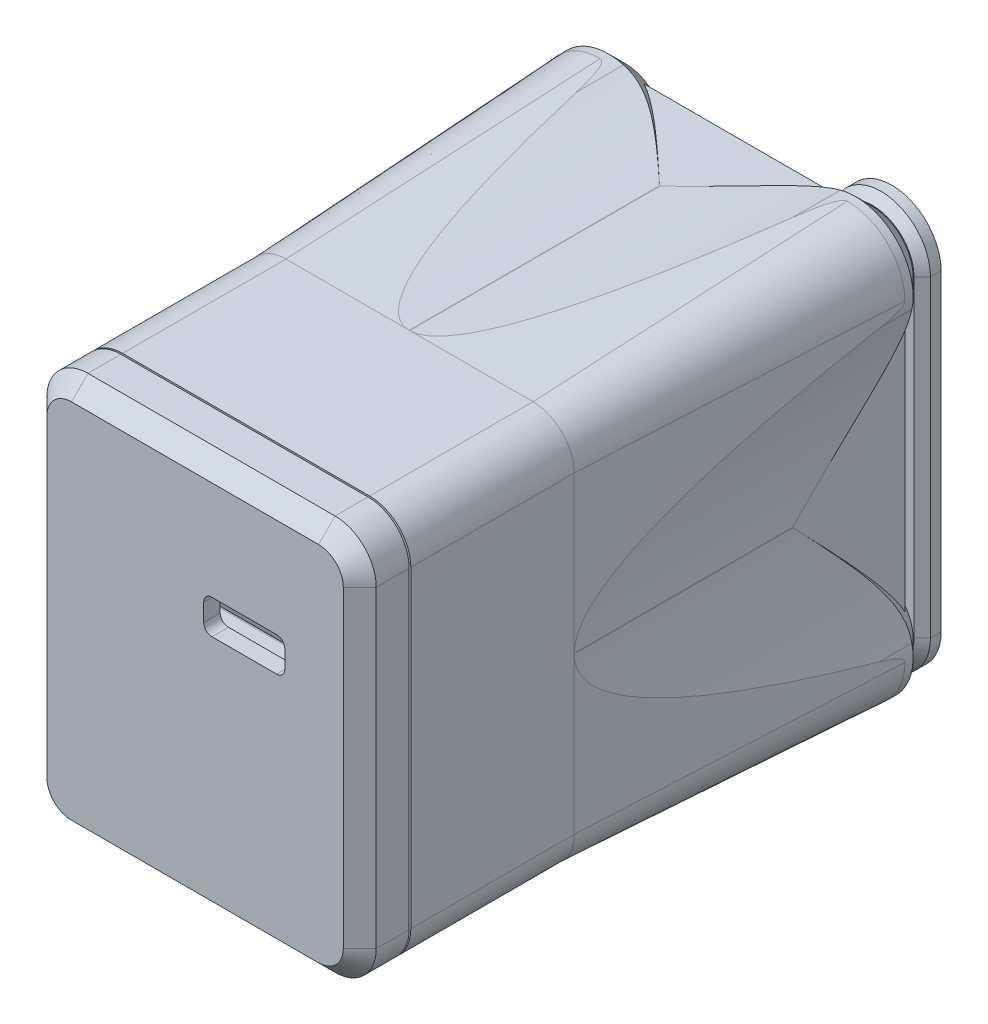
SolidWorks part; units mm, degrees
ref_plane "Front" through (0, 0, 0) normal (0, 0, 1) x (1, 0, 0)
ref_plane "Top" through (0, 0, 0) normal (0, 1, 0) x (1, 0, 0)
ref_plane "Right" through (0, 0, 0) normal (1, 0, 0) x (0, 0, -1)
sketch "Sketch2" plane through (0, 0, 0) normal (0, 0, 1) x (1, 0, 0)
  line L1 (-20, -24) -> (20, -24)
  line L2 (-20, -24) -> (-20, 24)
  line L3 (-20, 24) -> (20, 24)
  line L4 (20, -24) -> (20, 24)
  line L5 (-20, -24) -> (20, 24) construction
  line L6 (-20, 24) -> (20, -24) construction
  point P0 (0, 0)
  dimension "D1" = 48
  dimension "D2" = 40
extrude "Boss-Extrude1" add sketch "Sketch2" along normal blind 61
fillet "Fillet1" radius 5 4 edges at (-20, -24, 30.5) (20, -24, 30.5) (20, 24, 30.5) (-20, 24, 30.5)
shell "Shell1" thickness 3
sketch "Sketch3" plane through (0, 0, 3) normal (0, 0, 1) x (1, 0, 0)
  line L0 (6.4, -5.1945) -> (6.4, -0.3945)
  line L1 (-6, -4.7945) -> (6, -4.7945) construction
  line L2 (-6, -4.7945) -> (-6, -0.7945) construction
  line L3 (-6, -0.7945) -> (6, -0.7945) construction
  line L4 (6, -4.7945) -> (6, -0.7945) construction
  line L5 (-6, -4.7945) -> (6, -0.7945) construction
  line L6 (-6, -0.7945) -> (6, -4.7945) construction
  line L7 (-6.4, -0.3945) -> (6.4, -0.3945)
  line L8 (-6.4, -5.1945) -> (-6.4, -0.3945)
  line L9 (-6.4, -5.1945) -> (6.4, -5.1945)
  point P0 (0, -2.7945)
  dimension "D1" = 12
  dimension "D2" = 4
  dimension "D3" = 0.4
extrude "Cut-Extrude1" cut sketch "Sketch3" against normal through all contours L2 L1 L4 L3
sketch "Sketch4" plane through (0, 0, 3) normal (0, 0, 1) x (1, 0, 0)
  line L0 (-15, -21) -> (15, -21) construction
  line L1 (17, -21) -> (-17, -21)
  line L2 (17, -21) -> (17, 3.6055)
  line L3 (17, 3.6055) -> (-17, 3.6055)
  line L4 (-17, -21) -> (-17, 3.6055)
  line L5 (-17, 19) -> (-17, -19) construction
  line L6 (6.4, -0.3945) -> (-6.4, -0.3945) construction
  line L11 (6.4, -5.1945) -> (6.4, -0.3945)
  line L12 (6.4, -0.3945) -> (-6.4, -0.3945)
  line L13 (-6.4, -0.3945) -> (-6.4, -5.1945)
  line L14 (-6.4, -5.1945) -> (6.4, -5.1945)
  line L15 (6.4, -5.1945) -> (6.4, -0.3945)
  line L16 (6.4, -0.3945) -> (-6.4, -0.3945)
  line L17 (-6.4, -0.3945) -> (-6.4, -5.1945)
  line L18 (-6.4, -5.1945) -> (6.4, -5.1945)
  dimension "D1" = 4
  dimension "D2" = 0
extrude "Boss-Extrude2" add sketch "Sketch4" along normal blind 3
sketch "Sketch5" plane through (0, 0, 0) normal (0, 0, -1) x (-1, 0, 0)
  line L1 (-8.5, -7.4741) -> (8.5, -7.4741)
  line L2 (-8.5, -7.4741) -> (-8.5, 1.5259)
  line L3 (-8.5, 1.5259) -> (8.5, 1.5259)
  line L4 (-6.4, -0.3945) -> (-6.4, -5.1945)
  line L5 (6.4, -0.3945) -> (-6.4, -0.3945)
  line L6 (6.4, -5.1945) -> (6.4, -0.3945)
  line L7 (-6.4, -5.1945) -> (6.4, -5.1945)
  line L8 (-6.4, -0.3945) -> (-6.4, -5.1945)
  line L9 (6.4, -0.3945) -> (-6.4, -0.3945)
  line L10 (6.4, -5.1945) -> (6.4, -0.3945)
  line L11 (-6.4, -5.1945) -> (6.4, -5.1945)
  line L12 (8.5, -7.4741) -> (8.5, 1.5259)
  line L13 (-8.5, -7.4741) -> (8.5, 1.5259) construction
  line L14 (-8.5, 1.5259) -> (8.5, -7.4741) construction
  point P3 (0, -2.9741)
  dimension "D2" = 9
  dimension "D3" = 17
  dimension "D4" = 2.1
  dimension "D5" = 1.9204
  dimension "D1" = 0
extrude "Cut-Extrude2" cut sketch "Sketch5" against normal blind 4
chamfer "Chamfer1" distance 2 angle 45 4 edges at (0, 1.5259, 0) (-8.5, -2.9741, 0) (0, -7.4741, 0) (8.5, -2.9741, 0)
sketch "Sketch7" plane through (0, 0, 61) normal (0, 0, 1) x (1, 0, 0)
  line L1 (15, 20.6) -> (-15, 20.6)
  line L2 (-16.6, 19) -> (-16.6, -19)
  line L3 (-15, -20.6) -> (15, -20.6)
  line L4 (-20, 19) -> (-20, -19)
  line L5 (-15, -24) -> (15, -24)
  line L6 (20, -19) -> (20, 19)
  line L7 (15, 24) -> (-15, 24)
  line L8 (-20, 19) -> (-20, -19)
  line L9 (-15, -24) -> (15, -24)
  line L10 (20, -19) -> (20, 19)
  line L11 (15, 24) -> (-15, 24)
  line L12 (16.6, -19) -> (16.6, 19)
  line L13 (-17, 19) -> (-17, -19)
  line L14 (15, 21) -> (-15, 21)
  line L15 (17, -19) -> (17, 19)
  line L16 (-15, -21) -> (15, -21)
  line L17 (-17, 19) -> (-17, -19)
  line L18 (15, 21) -> (-15, 21)
  line L19 (17, -19) -> (17, 19)
  line L20 (-15, -21) -> (15, -21)
  line L21 (14.6, 18.6) -> (-14.6, 18.6)
  line L22 (-14.6, 18.6) -> (-14.6, -18.6)
  line L23 (-14.6, -18.6) -> (14.6, -18.6)
  line L24 (14.6, -18.6) -> (14.6, 18.6)
  arc A0 (-15, 20.6) -> (-16.6, 19) centre (-15, 19) ccw
  arc A1 (-16.6, -19) -> (-15, -20.6) centre (-15, -19) ccw
  arc A2 (15, -20.6) -> (16.6, -19) centre (15, -19) ccw
  arc A3 (16.6, 19) -> (15, 20.6) centre (15, 19) ccw
  arc A4 (-20, -19) -> (-15, -24) centre (-15, -19) ccw
  arc A5 (15, -24) -> (20, -19) centre (15, -19) ccw
  arc A6 (20, 19) -> (15, 24) centre (15, 19) ccw
  arc A7 (-15, 24) -> (-20, 19) centre (-15, 19) ccw
  arc A8 (-20, -19) -> (-15, -24) centre (-15, -19) ccw
  arc A9 (15, -24) -> (20, -19) centre (15, -19) ccw
  arc A10 (20, 19) -> (15, 24) centre (15, 19) ccw
  arc A11 (-15, 24) -> (-20, 19) centre (-15, 19) ccw
  arc A12 (-15, 21) -> (-17, 19) centre (-15, 19) ccw
  arc A13 (17, 19) -> (15, 21) centre (15, 19) ccw
  arc A14 (15, -21) -> (17, -19) centre (15, -19) ccw
  arc A15 (-17, -19) -> (-15, -21) centre (-15, -19) ccw
  arc A16 (-15, 21) -> (-17, 19) centre (-15, 19) ccw
  arc A17 (17, 19) -> (15, 21) centre (15, 19) ccw
  arc A18 (15, -21) -> (17, -19) centre (15, -19) ccw
  arc A19 (-17, -19) -> (-15, -21) centre (-15, -19) ccw
  arc A20 (-14.6, 18.6) -> (-14.6, 18.6) centre (-14.6, 18.6) ccw
  arc A21 (-14.6, -18.6) -> (-14.6, -18.6) centre (-14.6, -18.6) ccw
  arc A22 (14.6, -18.6) -> (14.6, -18.6) centre (14.6, -18.6) ccw
  arc A23 (14.6, 18.6) -> (14.6, 18.6) centre (14.6, 18.6) ccw
  dimension "D1" = 0
  dimension "D2" = 0
  dimension "D3" = 0.4
  dimension "D4" = 2
extrude "Boss-Extrude3" add sketch "Sketch7" against normal blind 3 and the other way blind 0.2 separate body contours L12 A3 L1 A0 L2 A1 L3 A2 A23 L24 A22 L23 A21 L22 A20 L21
sketch "Sketch8" plane through (0, 0, 61.2) normal (0, 0, 1) x (1, 0, 0)
  line L4 (-20, 19) -> (-20, -19)
  line L5 (-15, -24) -> (15, -24)
  line L6 (20, -19) -> (20, 19)
  line L7 (15, 24) -> (-15, 24)
  line L8 (-20, 19) -> (-20, -19)
  line L9 (-15, -24) -> (15, -24)
  line L10 (20, -19) -> (20, 19)
  line L11 (15, 24) -> (-15, 24)
  arc A4 (-20, -19) -> (-15, -24) centre (-15, -19) ccw
  arc A5 (15, -24) -> (20, -19) centre (15, -19) ccw
  arc A6 (20, 19) -> (15, 24) centre (15, 19) ccw
  arc A7 (-15, 24) -> (-20, 19) centre (-15, 19) ccw
  arc A8 (-20, -19) -> (-15, -24) centre (-15, -19) ccw
  arc A9 (15, -24) -> (20, -19) centre (15, -19) ccw
  arc A10 (20, 19) -> (15, 24) centre (15, 19) ccw
  arc A11 (-15, 24) -> (-20, 19) centre (-15, 19) ccw
  dimension "D1" = 0
extrude "Boss-Extrude4" add sketch "Sketch8" along normal blind 6
chamfer "Chamfer2" distance 2 angle 45 8 edges at (0, 24, 67.2) (20, 0, 67.2) (18.5355, 22.5355, 67.2) (18.5355, -22.5355, 67.2) (0, -24, 67.2) (-18.5355, 22.5355, 67.2) (-18.5355, -22.5355, 67.2) (-20, 0, 67.2)
fillet "Fillet2" radius 1 4 edges at (14.6, -18.6, 59.6) (14.6, 18.6, 59.6) (-14.6, -18.6, 59.6) (-14.6, 18.6, 59.6)
chamfer "Chamfer3" distance 3 angle 45 1 edges at (0, 3.6055, 3)
fillet "Fillet3" radius 3 1 edges at (0, 6.6055, 3)
sketch "Sketch9" plane through (0, 0, 61.2) normal (0, 0, -1) x (-1, 0, 0)
  line L0 (1.05, 9.9738) -> (10.9, 9.9738) construction
  line L1 (1.55, 6.3238) -> (10.4, 6.3238) construction
  line L2 (1.55, 6.3238) -> (1.55, 9.4738) construction
  line L3 (1.55, 9.4738) -> (10.4, 9.4738) construction
  line L4 (10.4, 6.3238) -> (10.4, 9.4738) construction
  line L5 (1.55, 6.3238) -> (10.4, 9.4738) construction
  line L6 (1.55, 9.4738) -> (10.4, 6.3238) construction
  line L7 (10.9, 5.8238) -> (10.9, 9.9738) construction
  line L8 (1.05, 5.8238) -> (10.9, 5.8238) construction
  line L9 (1.05, 5.8238) -> (1.05, 9.9738) construction
  line L10 (5.975, 7.8988) -> (-5.975, 7.8988) construction
  line L12 (-10.4, 6.3238) -> (-1.55, 6.3238) construction
  line L13 (-10.4, 6.3238) -> (-10.4, 9.4738) construction
  line L14 (-10.4, 9.4738) -> (-1.55, 9.4738) construction
  line L15 (-1.55, 6.3238) -> (-1.55, 9.4738) construction
  line L16 (-10.4, 6.3238) -> (-1.55, 9.4738) construction
  line L17 (-10.4, 9.4738) -> (-1.55, 6.3238) construction
  line L22 (-10.9, 5.8238) -> (-1.05, 5.8238)
  line L23 (-1.05, 5.8238) -> (-1.05, 9.9738)
  line L24 (-10.9, 9.9738) -> (-1.05, 9.9738)
  line L25 (-10.9, 5.8238) -> (-10.9, 9.9738)
  line L26 (0, 0) -> (0, 7.8988) construction
  point P0 (5.975, 7.8988)
  point P14 (-5.975, 7.8988)
  dimension "D1" = 3.15
  dimension "D2" = 8.85
  dimension "D4" = 3.15
  dimension "D5" = 8.85
  dimension "D7" = 20.8
  dimension "D3" = 0.5
  dimension "D6" = 0.5
extrude "Cut-Extrude3" cut sketch "Sketch9" against normal through all
fillet "Fillet4" radius 1 4 edges at (10.9, 5.8238, 64.2) (10.9, 9.9738, 64.2) (1.05, 9.9738, 64.2) (1.05, 5.8238, 64.2)
sketch "Sketch12" plane through (0, 0, 61.2) normal (0, 0, -1) x (-1, 0, 0)
  line L1 (-14.6, 3.8238) -> (14.6, 3.8238)
  line L2 (-14.6, 3.8238) -> (-14.6, 10.0951)
  line L3 (-14.6, 10.0951) -> (14.6, 10.0951)
  line L4 (14.6, 3.8238) -> (14.6, 10.0951)
  line L5 (-14.6, 3.8238) -> (14.6, 10.0951) construction
  line L6 (-14.6, 10.0951) -> (14.6, 3.8238) construction
  line L7 (-14.6, -17.6) -> (-14.6, 17.6) construction
  line L8 (14.6, 17.6) -> (14.6, -17.6) construction
  point P0 (0, 6.9595)
extrude "Cut-Extrude4" cut sketch "Sketch12" against normal offset from surface (4 mm away) 2 up to face at (5.975, 7.8988, 67.2)
chamfer "Chamfer4" distance 4 angle 45 1 edges at (0, 10.0951, 61.2)
fillet "Fillet5" radius 0.5 2 edges at (0, 14.0951, 61.2) (0, 3.8238, 61.2)
sketch "Sketch13" plane through (0, -24, 0) normal (0, -1, 0) x (1, 0, 0)
  line L0 (0, 0) -> (0, 48) construction
  line L1 (-2.6382, 42.5) -> (2.6382, 42.5)
  line L2 (-2.6382, 53.5) -> (2.6382, 53.5)
  circle A0 centre (0, 48) radius 6.1
  dimension "D1" = 12.2
  dimension "D2" = 11
  dimension "D3" = 48
extrude "Cut-Extrude5" cut sketch "Sketch13" against normal blind 4
sketch "Sketch14" plane through (0, 0, 0) normal (0, 0, -1) x (-1, 0, 0)
  circle A0 centre (15, 19) radius 3.25 construction
  circle A1 centre (15, 19) radius 3.65
  circle A2 centre (-15, 19) radius 3.65
  circle A3 centre (-15, -19) radius 3.65
  circle A4 centre (15, -19) radius 3.65
  dimension "D1" = 6.5
  dimension "D3" = 7.3
  dimension "D4" = 7.3
  dimension "D5" = 7.3
  dimension "D2" = 0.4
extrude "Cut-Extrude6" cut sketch "Sketch14" against normal blind 1.7
sketch "Sketch15" plane through (0, 0, 0) normal (0, 0, -1) x (-1, 0, 0)
  circle A0 centre (15, 19) radius 7
  circle A1 centre (15, 19) radius 5
  circle A2 centre (-15, 19) radius 7
  circle A3 centre (-15, 19) radius 5
  circle A4 centre (15, -19) radius 5
  circle A5 centre (15, -19) radius 7
  circle A6 centre (-15, -19) radius 5
  circle A7 centre (-15, -19) radius 7
  arc A8 (-20, -19) -> (-15, -24) centre (-15, -19) ccw construction
  arc A9 (15, -24) -> (20, -19) centre (15, -19) ccw construction
  arc A10 (20, 19) -> (15, 24) centre (15, 19) ccw construction
  arc A11 (-15, 24) -> (-20, 19) centre (-15, 19) ccw construction
  dimension "D1" = 2
  dimension "D2" = 2
  dimension "D3" = 2
  dimension "D4" = 2
extrude "Boss-Extrude5" add sketch "Sketch15" against normal blind 3
chamfer "Chamfer5" distance 1 angle 45 4 edges at (0, 24, 0) (-20, 0, 0) (0, -24, 0) (20, 0, 0)
chamfer "Chamfer6" distance 2 angle 45 4 edges at (19.9497, 23.9497, 0) (-19.9497, 23.9497, 0) (-19.9497, -23.9497, 0) (19.9497, -23.9497, 0)
chamfer "Chamfer8" distance 2 angle 87 12 edges at (-20, 16.5505, 3) (-12.5505, 24, 3) (-18.5355, 22.5355, 3) (12.5505, 24, 3) (20, 16.5505, 3) (18.5355, 22.5355, 3) (-20, -16.5505, 3) (-12.5505, -24, 3) (-18.5355, -22.5355, 3) (20, -16.5505, 3) (12.5505, -24, 3) (18.5355, -22.5355, 3)
fillet "Fillet7" radius 84 4 edges at (-20, -14.101, 21.5811) (-20, 14.101, 21.5811) (20, 14.101, 21.5811) (20, -14.101, 21.5811)
fillet "Fillet8" radius 50 4 edges at (10.101, -24, 21.5811) (-10.101, -24, 21.5811) (-10.101, 24, 21.5811) (10.101, 24, 21.5811)
sketch "Sketch16" plane through (0, 0, 0) normal (0, 0, -1) x (-1, 0, 0)
  line L0 (0, 0) -> (0, 5.0259) construction
  line L1 (-10.5, 3.5259) -> (10.5, 3.5259)
  line L2 (-10.5, 3.5259) -> (-10.5, 6.5259)
  line L3 (-10.5, 6.5259) -> (10.5, 6.5259)
  line L4 (10.5, 3.5259) -> (10.5, 6.5259)
  line L5 (-10.5, 3.5259) -> (10.5, 6.5259) construction
  line L6 (-10.5, 6.5259) -> (10.5, 3.5259) construction
  line L7 (-10.5, 3.5259) -> (10.5, 3.5259) construction
  line L8 (10.5, 3.5259) -> (10.5, -9.4741) construction
  point P0 (0, 5.0259)
  dimension "D2" = 3
extrude "Cut-Extrude7" cut sketch "Sketch16" against normal blind 10 contours L3 L4 L1 L2
sketch "Sketch17" plane through (0, 0, 61.2) normal (0, 0, -1) x (-1, 0, 0)
  line L0 (-14.6, 3.8238) -> (14.6, 3.8238) construction
  line L1 (14.6, 3.8238) -> (7.6004, 3.8238)
  line L2 (14.6, 3.8238) -> (14.6, -3.1298)
  line L3 (14.6, -3.1298) -> (7.6004, -3.1298)
  line L4 (7.6004, 3.8238) -> (7.6004, -3.1298)
  line L5 (14.6, 17.6) -> (14.6, -17.6) construction
extrude "Cut-Extrude8" cut sketch "Sketch17" against normal up to surface (4 mm away) up to face at (0, 6.9595, 65.2)
chamfer "Chamfer9" distance 1 angle 45 2 edges at (-11.1002, -3.1298, 61.2) (-7.6004, 0.097, 61.2)
sketch "Sketch18" plane through (0, 0, 0) normal (0, 0, -1) x (-1, 0, 0)
  line L0 (-15, 19) -> (-15, -19) construction
  line L1 (-9, 19) -> (-9, -19)
  line L2 (-21, 19) -> (-21, -19)
  arc A0 (-9, 19) -> (-21, 19) centre (-15, 19) ccw
  arc A1 (-21, -19) -> (-9, -19) centre (-15, -19) ccw
  point P2 (-15, 0)
  dimension "D1" = 6
extrude "Boss-Extrude7" add sketch "Sketch18" along normal blind 2.3 from offset 0.1 separate body
sketch "Sketch19" plane through (0, 0, -2.4) normal (0, 0, -1) x (-1, 0, 0)
  circle A0 centre (-15, 19) radius 3.65
  circle A1 centre (-15, -19) radius 3.65
  dimension "D1" = 7.3
  dimension "D2" = 7.3
extrude "Cut-Extrude9" cut sketch "Sketch19" against normal blind 1.7
chamfer "Chamfer10" distance 1 angle 45 4 edges at (9, 0, -0.1) (15, 25, -0.1) (15, -25, -0.1) (21, 0, -0.1)
